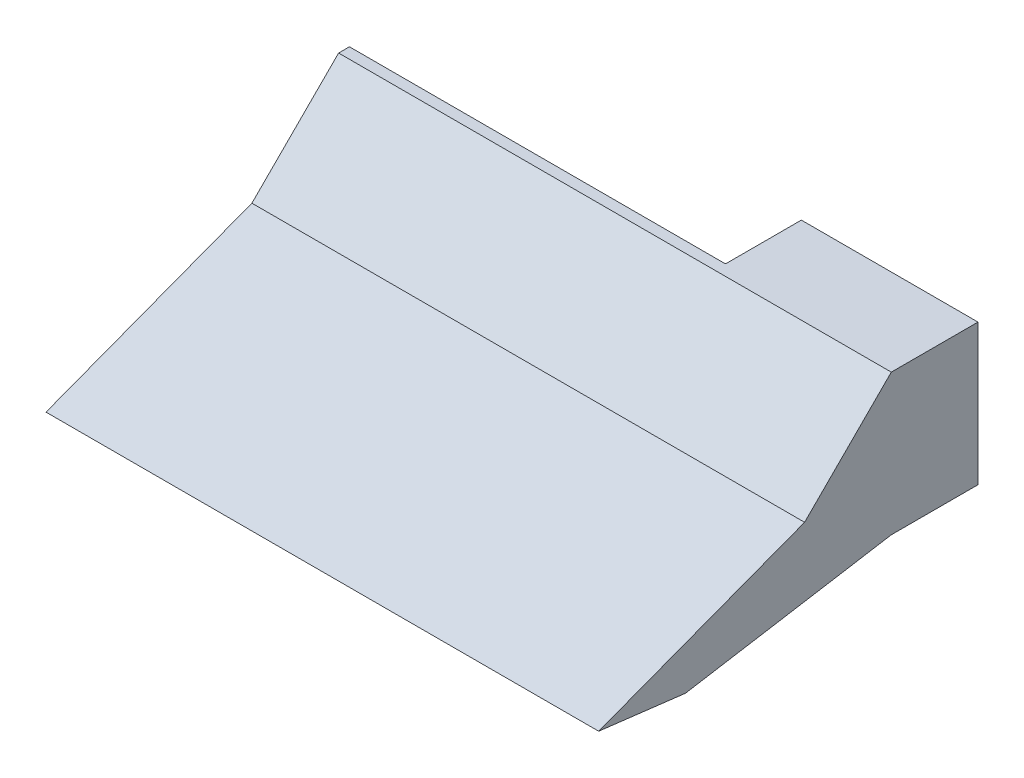
SolidWorks part; units mm, degrees
ref_plane "Front" through (0, 0, 0) normal (0, 0, 1) x (1, 0, 0)
ref_plane "Top" through (0, 0, 0) normal (0, 1, 0) x (1, 0, 0)
ref_plane "Right" through (0, 0, 0) normal (1, 0, 0) x (0, 0, -1)
sketch "Sketch2" plane through (0, 0, 0) normal (0, 0, 1) x (1, 0, 0)
  line L0 (0, 0) -> (36.0213, 0) construction
  line L1 (-8.15, 6.5) -> (8.15, 6.5)
  line L2 (-8.15, 6.5) -> (-8.15, -6.5)
  line L3 (-8.15, -6.5) -> (8.15, -6.5)
  line L4 (8.15, 6.5) -> (8.15, -6.5)
  line L5 (0, 0) -> (0, 33.6574) construction
  line L7 (-7.15, 5.5) -> (7.15, 5.5)
  line L8 (-7.15, 5.5) -> (-7.15, -5.5)
  line L9 (-7.15, -5.5) -> (7.15, -5.5)
  line L10 (7.15, 5.5) -> (7.15, -5.5)
  point P9 (0, 6.5)
  point P12 (8.15, 0)
  dimension "D1" = 16.3
  dimension "D2" = 13
  dimension "D3" = 1
  dimension "D4" = 1
  dimension "D5" = 1
  dimension "D6" = 1
extrude "Boss-Extrude1" add sketch "Sketch2" along normal blind 7
sketch "Sketch3" plane through (0, 0, 7) normal (0, 0, 1) x (1, 0, 0)
  line L1 (-8.15, 6.5) -> (42.85, 6.5)
  line L2 (-8.15, 6.5) -> (-8.15, -6.5)
  line L3 (-8.15, -6.5) -> (42.85, -6.5)
  line L4 (42.85, 6.5) -> (42.85, -6.5)
  line L5 (-7.15, 5.5) -> (7.15, 5.5)
  line L6 (-7.15, 5.5) -> (-7.15, -5.5)
  line L7 (-7.15, -5.5) -> (7.15, -5.5)
  line L8 (7.15, 5.5) -> (7.15, -5.5)
  dimension "D1" = 51
extrude "Boss-Extrude2" add sketch "Sketch3" along normal blind 1
sketch "Sketch4" plane through (-8.15, 0, 0) normal (-1, 0, 0) x (0, 0, 1)
  line L0 (8, 6.5) -> (16, -1.5)
  line L1 (8, -6.5) -> (14, -7.5)
  line L2 (14, -7.5) -> (27, -9.6667)
  line L3 (16, -1.5) -> (27, -5.6667)
  line L4 (27, -5.6667) -> (35, -8.697)
  line L5 (35, -8.697) -> (27, -9.6667)
  line L6 (8, 6.5) -> (8, -6.5)
  dimension "D1" = 6
  dimension "D2" = 6
  dimension "D3" = 1
  dimension "D4" = 45
  dimension "D5" = 13
  dimension "D6" = 11
  dimension "D7" = 4
  dimension "D8" = 8
extrude "Boss-Extrude3" add sketch "Sketch4" against normal blind 1
pattern_linear "LPattern1" count 2 spacing 50 along (1, 0, 0) of "Boss-Extrude3"
sketch "Sketch5" plane through (-7.15, 0, 0) normal (1, 0, 0) x (0, 0, -1)
  line L0 (-8, 5.5) -> (-16, -2.5)
  line L1 (-16, -2.5) -> (-33, -8.9394)
  line L2 (-27, -9.6667) -> (-35, -8.697) construction
  line L3 (-27, -9.6667) -> (-27, -1.587) construction
  line L6 (-35, -8.697) -> (-16, -1.5) construction
  line L7 (-16, -1.5) -> (-16, -4.4914) construction
  line L9 (-8, -5.5) -> (-27, -8.6667)
  line L10 (-8, -6.5) -> (-27, -9.6667) construction
  line L11 (-27, -8.6667) -> (-27, -9.6667)
  line L12 (-27, -9.6667) -> (-8, -6.5)
  line L13 (-8, -6.5) -> (-8, -5.5)
  line L14 (-33, -8.9394) -> (-35, -8.697)
  line L15 (-35, -8.697) -> (-16, -1.5)
  line L16 (-16, -1.5) -> (-8, 6.5)
  line L17 (-8, 6.5) -> (-8, 5.5)
  dimension "D1" = 1
extrude "Boss-Extrude4" add sketch "Sketch5" along normal up to next
mirror "Mirror2" about plane through (-8.15, 6.5, 7) normal (1, 0, 0) of bodies 105
delete or keep bodies "Body-Delete1" type delete bodies bodies 105
equation "\"wall_thicknes\"= 1"
equation "\"D3@Sketch2\"=\"wall_thicknes\""
equation "\"D4@Sketch2\"=\"wall_thicknes\""
equation "\"D5@Sketch2\"=\"wall_thicknes\""
equation "\"D6@Sketch2\"=\"wall_thicknes\""
equation "\"D1@Boss-Extrude2\"=\"wall_thicknes\""
equation "\"D1@Boss-Extrude3\"=\"wall_thicknes\""
equation "\"D1@Sketch5\"=\"wall_thicknes\""
